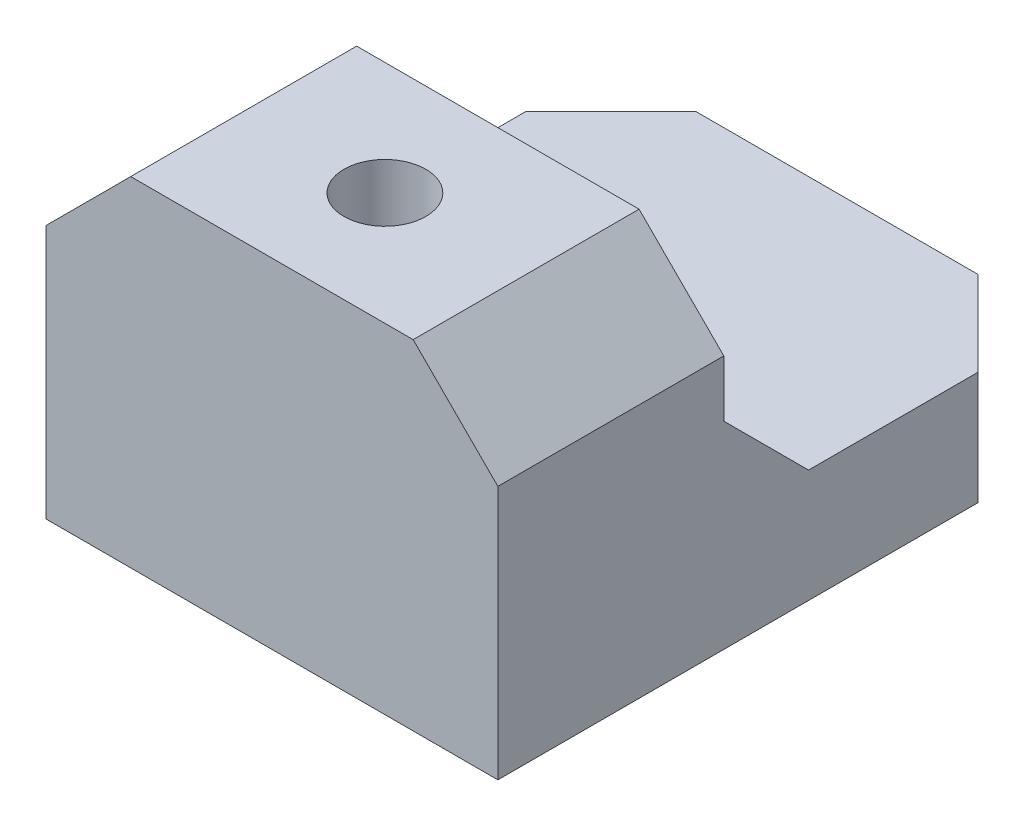
SolidWorks part; units mm, degrees
ref_plane "前视基准面" through (0, 0, 0) normal (0, 0, 1) x (1, 0, 0)
ref_plane "上视基准面" through (0, 0, 0) normal (0, 1, 0) x (1, 0, 0)
ref_plane "右视基准面" through (0, 0, 0) normal (1, 0, 0) x (0, 0, -1)
other "Configuration Table"
sketch "草图1" plane through (0, 0, 0) normal (0, 1, 0) x (1, 0, 0)
  line L1 (0, 0) -> (16, 0)
  line L2 (0, 0) -> (0, 20)
  line L3 (0, 20) -> (16, 20)
  line L4 (16, 0) -> (16, 20)
  dimension "D1" = 20
  dimension "D2" = 16
extrude "凸台-拉伸1" add sketch "草图1" along normal blind 4
sketch "草图2" plane through (0, 4, 0) normal (0, 1, 0) x (1, 0, 0)
  line L0 (16, 20) -> (0, 20) construction
  line L1 (0, 20) -> (0, 0) construction
  circle A0 centre (8, 12) radius 1.65
  dimension "D1" = 3.3
  dimension "D3" = 8
  dimension "D2" = 8
extrude "切除-拉伸1" cut sketch "草图2" against normal blind 4
sketch "草图3" plane through (0, 4, 0) normal (0, 1, 0) x (1, 0, 0)
  line L0 (16, 0) -> (16, 20) construction
  line L1 (0, 0) -> (16, 0)
  line L2 (0, 0) -> (0, 8)
  line L3 (0, 8) -> (16, 8)
  line L4 (16, 0) -> (16, 8)
  dimension "D1" = 8
extrude "凸台-拉伸2" add sketch "草图3" along normal blind 8
sketch "草图4" plane through (0, 12, 0) normal (0, 1, 0) x (1, 0, 0)
  line L0 (0, 0) -> (16, 0) construction
  line L1 (0, 8) -> (0, 0) construction
  circle A0 centre (8, 4) radius 1.45
  dimension "D1" = 2.9
  dimension "D2" = 4
  dimension "D3" = 8
extrude "切除-拉伸2" cut sketch "草图4" against normal through all
chamfer "倒角1" distance 3 angle 45 2 edges at (0, 2, -20) (16, 2, -20)
chamfer "倒角2" distance 3 angle 45 1 edges at (8, 4, -8)
chamfer "倒角3" distance 3 angle 45 2 edges at (0, 12, -4) (16, 12, -4)
sketch "草图6" plane through (0, 4, 0) normal (0, 1, 0) x (1, 0, 0)
  circle A0 centre (8, 12) radius 3
  dimension "D1" = 6
extrude "切除-拉伸3" cut sketch "草图6" along normal through all
